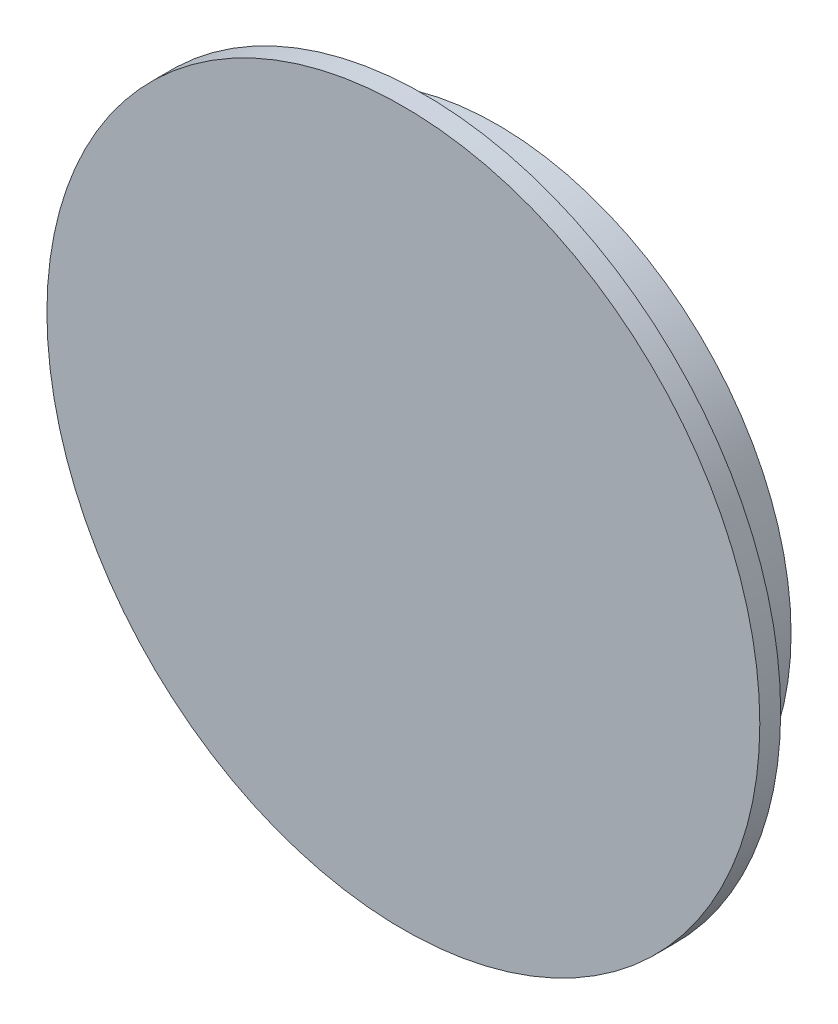
SolidWorks part; units mm, degrees
material "Custom Plastic"
ref_plane "X-Y Datum" through (0, 0, 0) normal (0, 0, 1) x (1, 0, 0)
ref_plane "X-Z Datum" through (0, 0, 0) normal (0, 1, 0) x (1, 0, 0)
ref_plane "Y-Z Datum" through (0, 0, 0) normal (1, 0, 0) x (0, 0, -1)
sketch "Sketch1" plane through (0, 0, 0) normal (0, 0, 1) x (1, 0, 0)
  circle A0 centre (0, 0) radius 14.1
  circle A1 centre (0, 0) radius 12.6
  circle A2 centre (0, 0) radius 17.1
  dimension "D1" = 28.2
  dimension "D2" = 1.5
  dimension "D3" = 3
extrude "Boss-Extrude1" add sketch "Sketch1" along normal blind 3.5 contours A0 A1 region at (-13.7012, 0, 0)
sketch "Sketch2" plane through (0, 0, 3.5) normal (0, 0, 1) x (1, 0, 0)
  circle A1 centre (0, 0) radius 17.1
  circle A2 centre (0, 0) radius 17.1
  circle A3 centre (0, 0) radius 12.6
  circle A4 centre (0, 0) radius 12.6
  circle A5 centre (0, 0) radius 14.1
  circle A6 centre (0, 0) radius 14.1
  circle M4 centre (0, 0) radius 12.6
  circle M5 centre (0, 0) radius 14.1
  dimension "D1" = 0
  dimension "D2" = 0
  dimension "D3" = 0
extrude "Boss-Extrude2" add sketch "Sketch2" along normal blind 1 contours M4 | M5 M4 | A2 M5 region at (-16.6163, 0, 3.5) region at (0, 0, 3.5) region at (-13.7012, 0, 3.5)
